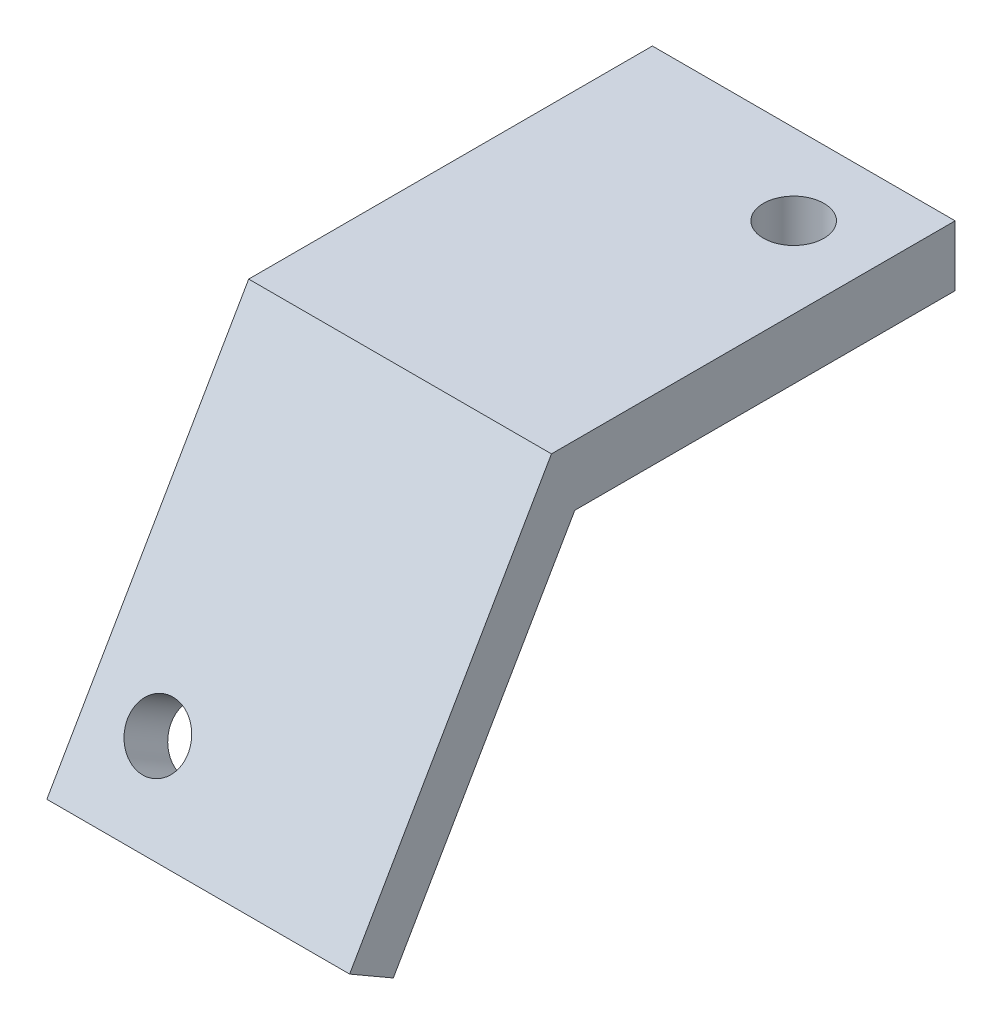
SolidWorks part; units mm, degrees
ref_plane "Front Plane" through (0, 0, 0) normal (0, 0, 1) x (1, 0, 0)
ref_plane "Top Plane" through (0, 0, 0) normal (0, 1, 0) x (1, 0, 0)
ref_plane "Right Plane" through (0, 0, 0) normal (1, 0, 0) x (0, 0, -1)
sketch "Sketch1" plane through (0, 0, 0) normal (0, 1, 0) x (1, 0, 0)
  line L1 (-7.5, -10) -> (7.5, -10)
  line L2 (-7.5, -10) -> (-7.5, 10)
  line L3 (-7.5, 10) -> (7.5, 10)
  line L4 (7.5, -10) -> (7.5, 10)
  line L5 (-7.5, -10) -> (7.5, 10) construction
  line L6 (-7.5, 10) -> (7.5, -10) construction
  circle A0 centre (3.5, 6) radius 1.5
  point P0 (0, 0)
  dimension "D3" = 3
  dimension "D1" = 15
  dimension "D2" = 20
  dimension "D4" = 4
  dimension "D5" = 4
extrude "Boss-Extrude1" add sketch "Sketch1" along normal blind 3
ref_plane "Plane1" through (0, -2.0801, 1.201) normal (0, 0.866, -0.5) x (1, 0, 0)
sketch "Sketch2" plane through (0, -2.0801, 1.201) normal (0, 0.866, -0.5) x (1, 0, 0)
  line L0 (-7.5, -10.1603) -> (-7.5, -8.6603) construction
  line L1 (-7.5, -7.6603) -> (7.5, -7.6603)
  line L2 (-7.5, -7.6603) -> (-7.5, -10.1603)
  line L3 (-7.5, -10.1603) -> (7.5, -10.1603)
  line L4 (7.5, -7.6603) -> (7.5, -10.1603)
  line L6 (-7.5, -8.6603) -> (7.5, -8.6603) construction
  dimension "D1" = 1
extrude "Boss-Extrude2" add sketch "Sketch2" against normal blind 20
sketch "Sketch3" plane through (0, 5.0801, 8.799) normal (0, 0.5, 0.866) x (1, 0, 0)
  line L1 (-7.5, -22.4019) -> (7.5, -22.4019) construction
  circle A0 centre (-4, -18.4019) radius 1.5
  ellipse E0 centre (3.5, 5.5981) end of major axis (5, 5.5981) minor radius 0.75 construction
  dimension "D1" = 3
  dimension "D2" = 4
  dimension "D3" = 7.5
extrude "Cut-Extrude1" cut sketch "Sketch3" against normal blind 10
